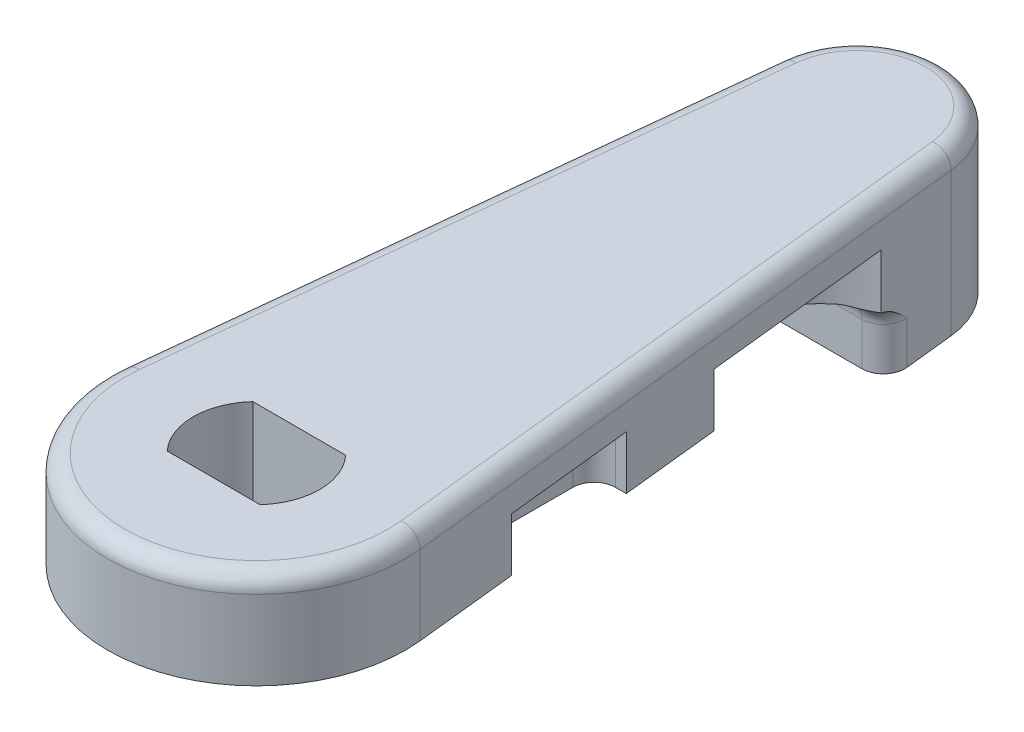
SolidWorks part; units mm, degrees
ref_plane "Front Plane" through (0, 0, 0) normal (0, 0, 1) x (1, 0, 0)
ref_plane "Top Plane" through (0, 0, 0) normal (0, 1, 0) x (1, 0, 0)
ref_plane "Right Plane" through (0, 0, 0) normal (1, 0, 0) x (0, 0, -1)
sketch "Sketch1" plane through (0, 0, 0) normal (0, 1, 0) x (1, 0, 0)
  line L1 (-3.4903, -2) -> (3.4903, -2)
  line L2 (-3.4903, -2) -> (-3.4903, 2)
  line L3 (-3.4903, 2) -> (3.4903, 2)
  line L4 (3.4903, -2) -> (3.4903, 2)
  line L5 (-3.4903, -2) -> (3.4903, 2) construction
  line L6 (-3.4903, 2) -> (3.4903, -2) construction
  circle A0 centre (0, 0) radius 2.95
  circle A1 centre (0, 0) radius 6.95
  dimension "D1" = 5.9
  dimension "D2" = 4
  dimension "D3" = 4
extrude "Boss-Extrude1" add sketch "Sketch1" along normal blind 6 contours A1 A0 L3 L4 L1 L2 | L3 A0 | L1 A0 | A0 L3 L2 L1 | A0 L1 L4 L3 region at (-3.0648, 0, 0) region at (0, 0, 2.3858) region at (3.0648, 0, 0) region at (0, 0, -2.3858) region at (-6.7534, 0, 0)
sketch "Sketch2" plane through (0, 6, 0) normal (0, 1, 0) x (1, 0, 0)
  line L0 (0, 0) -> (0, 28.05) construction
  line L1 (-3.9778, 28.4707) -> (-6.9115, 0.7309)
  line L2 (3.9778, 28.4707) -> (6.9115, 0.7309)
  circle A0 centre (0, 28.05) radius 4
  circle A3 centre (0, 0) radius 6.95 construction
  circle A4 centre (0, 0) radius 6.95
  circle M7 centre (0, 0) radius 6.95
  dimension "D1" = 39
  dimension "D2" = 8
  dimension "D3" = 28.05
extrude "Boss-Extrude2" add sketch "Sketch2" against normal up to surface (6 mm away) contours A4 L0 A0 L1 | L0 L2 A0 M7 | A0 region at (-2.9071, 6, -14.7075) region at (2.9071, 6, -14.7075) region at (-2.8893, 6, -25.4501) up to face at (0, 0, 0)
sketch "Sketch3" plane through (0, 0, 0) normal (0, -1, 0) x (1, 0, 0)
  line L0 (6.9115, -0.7309) -> (3.9778, -28.4707) construction
  line L1 (-6.9115, -0.7309) -> (-3.9778, -28.4707) construction
  line L2 (6.9115, -0.7309) -> (3.9778, -28.4707)
  line L3 (-6.9115, -0.7309) -> (-3.9778, -28.4707)
  line L4 (-4.3396, -25.05) -> (4.3396, -25.05)
  arc A0 (-3.9778, -28.4707) -> (3.9778, -28.4707) centre (0, -28.05) ccw construction
  arc A1 (-3.9778, -28.4707) -> (3.9778, -28.4707) centre (0, -28.05) ccw
  arc M8 (-3.9778, -28.4707) -> (3.9778, -28.4707) centre (0, -28.05) ccw
  line M9 (3.9778, -28.4707) -> (6.9115, -0.7309)
  dimension "D1" = 7
extrude "Boss-Extrude3" add sketch "Sketch3" along normal blind 3 contours L4 L3 M8 M9 region at (0, 0, -28.1409)
fillet "Fillet1" radius 1 2 edges at (4.3396, -1.5, -25.05) (-4.3396, -1.5, -25.05)
sketch "Sketch4" plane through (0, 0, 0) normal (0, -1, 0) x (1, 0, 0)
  line L0 (-2.1685, -2) -> (2.1685, -2) construction
  line L1 (-10.1531, -5.5) -> (11.4826, -5.5)
  line L2 (-10.1531, -5.5) -> (-10.1531, -11.5)
  line L3 (-10.1531, -11.5) -> (11.4826, -11.5)
  line L4 (11.4826, -5.5) -> (11.4826, -11.5)
  dimension "D1" = 3.5
  dimension "D2" = 6
extrude "Cut-Extrude1" cut sketch "Sketch4" against normal blind 2.5
sketch "Sketch5" plane through (0, 0, 0) normal (0, -1, 0) x (1, 0, 0)
  line L0 (4.2726, -5.5) -> (4.2726, -11.5)
  line L4 (5.7726, -11.5) -> (6.4071, -5.5)
  line L5 (6.4071, -5.5) -> (-6.4071, -5.5)
  line L6 (-6.4071, -5.5) -> (-5.7726, -11.5)
  line L7 (-5.7726, -11.5) -> (5.7726, -11.5)
  line L8 (5.7726, -11.5) -> (6.4071, -5.5)
  line L9 (6.4071, -5.5) -> (-6.4071, -5.5)
  line L10 (-6.4071, -5.5) -> (-5.7726, -11.5)
  line L11 (-5.7726, -11.5) -> (5.7726, -11.5)
  line M6 (5.7726, -11.5) -> (-5.7726, -11.5)
  dimension "D2" = 1.5
  dimension "D1" = 0
extrude "Boss-Extrude4" add sketch "Sketch5" against normal up to surface (2.5 mm away) contours L9 L10 L0 M6 region at (-0.9103, 0, -8.4694) up to face at (0, 2.5, -8.5)
sketch "Sketch6" plane through (0, 6, 0) normal (0, 1, 0) x (1, 0, 0)
  line L2 (6.9115, 0.7309) -> (3.9778, 28.4707)
  line L3 (-3.9778, 28.4707) -> (-6.9115, 0.7309)
  line L4 (6.9115, 0.7309) -> (3.9778, 28.4707)
  line L5 (-3.9778, 28.4707) -> (-6.9115, 0.7309)
  arc A2 (-6.9115, 0.7309) -> (6.9115, 0.7309) centre (0, 0) ccw
  arc A3 (3.9778, 28.4707) -> (-3.9778, 28.4707) centre (0, 28.05) ccw
  arc A4 (-6.9115, 0.7309) -> (6.9115, 0.7309) centre (0, 0) ccw
  arc A5 (3.9778, 28.4707) -> (-3.9778, 28.4707) centre (0, 28.05) ccw
  dimension "D1" = 0
extrude "Cut-Extrude2" cut sketch "Sketch6" against normal blind 1.5
sketch "Sketch7" plane through (0, -3, 0) normal (0, -1, 0) x (1, 0, 0)
  line L3 (3.9778, -28.4707) -> (4.2227, -26.1552)
  line L4 (3.2282, -25.05) -> (-3.2282, -25.05)
  line L5 (-4.2227, -26.1552) -> (-3.9778, -28.4707)
  line L6 (3.9778, -28.4707) -> (4.2227, -26.1552)
  line L7 (3.2282, -25.05) -> (-3.2282, -25.05)
  line L8 (-4.2227, -26.1552) -> (-3.9778, -28.4707)
  circle A0 centre (0, 0) radius 28.5
  arc A3 (4.2227, -26.1552) -> (3.2282, -25.05) centre (3.2282, -26.05) ccw
  arc A4 (-3.2282, -25.05) -> (-4.2227, -26.1552) centre (-3.2282, -26.05) ccw
  arc A5 (-3.9778, -28.4707) -> (3.9778, -28.4707) centre (0, -28.05) ccw
  arc A6 (4.2227, -26.1552) -> (3.2282, -25.05) centre (3.2282, -26.05) ccw
  arc A7 (-3.2282, -25.05) -> (-4.2227, -26.1552) centre (-3.2282, -26.05) ccw
  arc A8 (-3.9778, -28.4707) -> (3.9778, -28.4707) centre (0, -28.05) ccw
  line M8 (3.9778, -28.4707) -> (4.2227, -26.1552)
  arc M9 (4.2227, -26.1552) -> (3.2282, -25.05) centre (3.2282, -26.05) ccw
  line M10 (3.2282, -25.05) -> (-3.2282, -25.05)
  arc M11 (-3.2282, -25.05) -> (-4.2227, -26.1552) centre (-3.2282, -26.05) ccw
  line M12 (-4.2227, -26.1552) -> (-3.9778, -28.4707)
  arc M13 (-3.9778, -28.4707) -> (3.9778, -28.4707) centre (0, -28.05) ccw
  dimension "D2" = 57
  dimension "D1" = 0
extrude "Boss-Extrude5" [suppressed] add sketch "Sketch7" along normal blind 1.5 contours A0 M13 M8 M9 M10 M11 M12
fillet "Fillet2" radius 1 2 edges at (4.2726, 1.25, -5.5) (4.2726, 1.25, -11.5)
fillet "Fillet3" radius 1 3 edges at (-3.9716, 0, -25.3811) (3.9716, 0, -25.3811) (0, 0, -25.05)
fillet "Fillet4" radius 0.8 4 edges at (0, 4.5, 6.95) (-5.4446, 4.5, -14.6008) (0, 4.5, -32.05) (5.4446, 4.5, -14.6008)
sketch "Sketch8" plane through (0, 0, 0) normal (0, -1, 0) x (1, 0, 0)
  line L0 (4.826, -20.4501) -> (15.3065, -21.5585) construction
  line L1 (5.7726, -11.5) -> (4.4049, -24.4327) construction
  circle A0 centre (5.8205, -20.5553) radius 4.5
  point P6 (6.27, -20.3123)
  dimension "D1" = 9
  dimension "D2" = 9
  dimension "D3" = 1
extrude "Cut-Extrude3" cut sketch "Sketch8" against normal blind 2.5 and the other way blind 1
